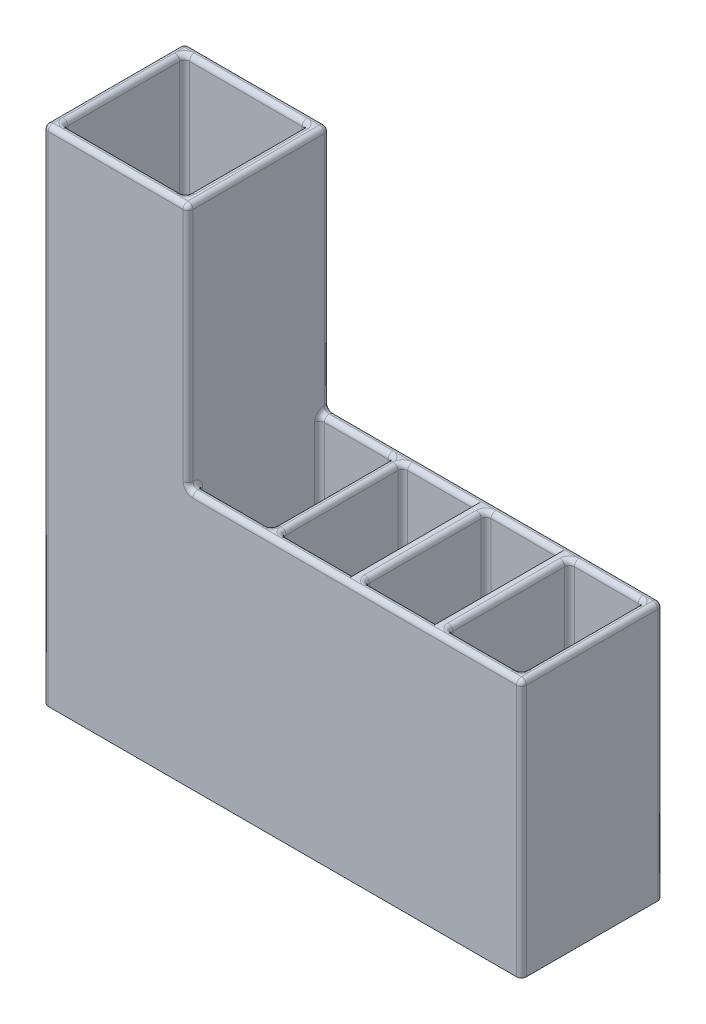
SolidWorks part; units mm, degrees
ref_plane "Front Plane" through (0, 0, 0) normal (0, 0, 1) x (1, 0, 0)
ref_plane "Top Plane" through (0, 0, 0) normal (0, 1, 0) x (1, 0, 0)
ref_plane "Right Plane" through (0, 0, 0) normal (1, 0, 0) x (0, 0, -1)
sketch "Sketch1" plane through (0, 0, 0) normal (0, 1, 0) x (1, 0, 0)
  line L0 (-61.9125, 18.288) -> (-59.3725, 15.748) construction
  line L1 (-61.9125, -18.288) -> (61.9125, -18.288)
  line L2 (-61.9125, -18.288) -> (-61.9125, 18.288)
  line L3 (-61.9125, 18.288) -> (61.9125, 18.288)
  line L4 (61.9125, -18.288) -> (61.9125, 18.288)
  line L5 (-61.9125, -18.288) -> (61.9125, 18.288) construction
  line L6 (-61.9125, 18.288) -> (61.9125, -18.288) construction
  line L7 (-59.3725, 15.748) -> (-27.6225, 15.748)
  line L8 (-59.3725, 15.748) -> (-59.3725, -15.748)
  line L9 (-59.3725, -15.748) -> (-27.6225, -15.748)
  line L10 (-27.6225, 15.748) -> (-27.6225, -15.748)
  line L11 (-59.3725, 15.748) -> (-27.6225, -15.748) construction
  line L12 (-59.3725, -15.748) -> (-27.6225, 15.748) construction
  line L13 (-61.9125, -18.288) -> (-59.3725, -15.748) construction
  line L14 (59.3725, 15.748) -> (61.9125, 18.288) construction
  line L15 (-24.4475, 15.748) -> (59.3725, 15.748)
  line L16 (-24.4475, 15.748) -> (-24.4475, -15.748)
  line L17 (-24.4475, -15.748) -> (59.3725, -15.748)
  line L18 (59.3725, 15.748) -> (59.3725, -15.748)
  line L19 (-27.6225, 15.748) -> (-24.4475, 15.748) construction
  point P0 (0, 0)
  point P6 (-43.4975, 0)
  dimension "D1" = 2.54
  dimension "D2" = 31.496
  dimension "D3" = 31.75
  dimension "D4" = 3.175
  dimension "D5" = 123.825
extrude "Boss-Extrude1" add sketch "Sketch1" along normal blind 127
sketch "Sketch2" plane through (0, 0, 0) normal (0, -1, 0) x (1, 0, 0)
  line L4 (61.9125, -18.288) -> (61.9125, 18.288)
  line L5 (61.9125, 18.288) -> (-61.9125, 18.288)
  line L6 (-61.9125, 18.288) -> (-61.9125, -18.288)
  line L7 (-61.9125, -18.288) -> (61.9125, -18.288)
  line L8 (61.9125, -18.288) -> (61.9125, 18.288)
  line L9 (61.9125, 18.288) -> (-61.9125, 18.288)
  line L10 (-61.9125, 18.288) -> (-61.9125, -18.288)
  line L11 (-61.9125, -18.288) -> (61.9125, -18.288)
  dimension "D1" = 0
extrude "Boss-Extrude2" add sketch "Sketch2" along normal blind 3.175
sketch "Sketch3" plane through (0, 127, 0) normal (0, 1, 0) x (1, 0, 0)
  line L0 (61.9125, 18.288) -> (-61.9125, 18.288) construction
  line L1 (61.9125, -18.288) -> (-24.4475, -18.288)
  line L2 (61.9125, -18.288) -> (61.9125, 18.288)
  line L3 (61.9125, 18.288) -> (-24.4475, 18.288)
  line L4 (-24.4475, -18.288) -> (-24.4475, 18.288)
  line L5 (-24.4475, 15.748) -> (-24.4475, -15.748) construction
extrude "Cut-Extrude1" cut sketch "Sketch3" against normal offset from surface (63.5 mm away) 63.5 up to face at (17.4625, 0, 0)
sketch "Sketch5" plane through (0, 0, 0) normal (0, 1, 0) x (1, 0, 0)
  line L0 (59.3725, 15.748) -> (-24.4475, 15.748) construction
  line L1 (-5.3975, 15.748) -> (-2.8575, 15.748)
  line L2 (-5.3975, 15.748) -> (-5.3975, -15.748)
  line L3 (-5.3975, -15.748) -> (-2.8575, -15.748)
  line L4 (-2.8575, 15.748) -> (-2.8575, -15.748)
  line L5 (59.3725, -15.748) -> (-24.4475, -15.748) construction
  line L6 (-24.4475, 15.748) -> (59.3725, 15.748) construction
  line L7 (16.1925, 15.748) -> (18.7325, 15.748)
  line L8 (16.1925, 15.748) -> (16.1925, -15.748)
  line L9 (16.1925, -15.748) -> (18.7325, -15.748)
  line L10 (18.7325, 15.748) -> (18.7325, -15.748)
  line L11 (37.7825, 15.748) -> (40.3225, 15.748)
  line L12 (37.7825, 15.748) -> (37.7825, -15.748)
  line L13 (37.7825, -15.748) -> (40.3225, -15.748)
  line L14 (40.3225, 15.748) -> (40.3225, -15.748)
  line L16 (-24.4475, 15.748) -> (-5.3975, -15.748) construction
  line L17 (-2.8575, -15.748) -> (16.1925, 15.748) construction
  line L18 (18.7325, 15.748) -> (37.7825, -15.748) construction
  line L19 (40.3225, -15.748) -> (59.3725, 15.748) construction
  dimension "D1" = 2.54
extrude "Boss-Extrude4" add sketch "Sketch5" along normal up to surface (63.5 mm away) up to face at (18.0975, 63.5, 0)
sketch "Sketch6" plane through (0, 0, 0) normal (0, 1, 0) x (1, 0, 0)
  line L0 (-59.3725, -15.748) -> (-27.6225, 15.748) construction
  line L1 (-2.8575, -15.748) -> (16.1925, 15.748) construction
  line L2 (40.3225, -15.748) -> (59.3725, 15.748) construction
  point P12 (-43.4975, 0)
  point P13 (6.6675, 0)
  point P14 (49.8475, 0)
fillet "Fillet1" radius 1.27 66 edges at (-24.4475, 95.25, 18.288) (-24.4475, 95.25, -18.288) (49.8475, 0, 15.748) (49.8475, 63.5, 15.748) (49.8475, 63.5, -15.748) (49.8475, 0, -15.748) (6.6675, 63.5, 15.748) (6.6675, 0, 15.748) (6.6675, 0, -15.748) (6.6675, 63.5, -15.748) (28.2575, 63.5, 15.748) (28.2575, 0, 15.748) (28.2575, 0, -15.748) (28.2575, 63.5, -15.748) (-43.4975, 127, 15.748) (-43.4975, 127, -15.748) (-14.9225, 63.5, 15.748) (-14.9225, 0, 15.748) (-14.9225, 0, -15.748) (-14.9225, 63.5, -15.748) (-61.9125, 127, 0) (-43.18, 127, -18.288) (-24.4475, 127, 0) (-43.18, 127, 18.288) (-24.4475, 0, 0) (-5.3975, 0, 0) (40.3225, 31.75, 15.748) (40.3225, 63.5, 0) (40.3225, 0, 0) (40.3225, 31.75, -15.748) (59.3725, 31.75, 15.748) (59.3725, 31.75, -15.748) (59.3725, 63.5, 0) (59.3725, 0, 0) (16.1925, 0, 0) (37.7825, 0, 0) (-2.8575, 0, 0) (-2.8575, 31.75, 15.748) (-2.8575, 63.5, 0) (-2.8575, 31.75, -15.748) (18.7325, 0, 0) (18.7325, 31.75, 15.748) (18.7325, 63.5, 0) (18.7325, 31.75, -15.748) (-27.6225, 63.5, -15.748) (-27.6225, 127, 0) (-27.6225, 63.5, 15.748) (-59.3725, 63.5, 15.748) (-59.3725, 127, 0) (-59.3725, 63.5, -15.748) (-43.4975, 0, -15.748) (-27.6225, 0, 0) (-43.4975, 0, 15.748) (-59.3725, 0, 0) (61.9125, 30.1625, 18.288) (-61.9125, 61.9125, -18.288) (-61.9125, 61.9125, 18.288) (18.7325, 63.5, -18.288) (18.7325, 63.5, 18.288) (61.9125, 63.5, 0) (61.9125, 30.1625, -18.288) (-5.3975, 63.5, 0) (-5.3975, 31.75, 15.748) (-24.4475, 31.75, 15.748) (-5.3975, 31.75, -15.748) (-24.4475, 31.75, -15.748)
hole_wizard "CSK for #10 Flat Head Machine Screw (100)1" positions "3DSketch1" profile "Sketch7" countersink size "#10" standard "ANSI Inch" end condition through all
sketch3d "3DSketch1"
  point P0 (-43.4975, 0, 0)
  point P3 (6.6675, 0, 0)
  point P6 (49.8475, 0, 0)
sketch "Sketch7" plane through (-43.4975, 0, 0) normal (1, 0, 0) x (0, 0, 1)
  line L0 (0, 0) -> (0, 3.175)
  line L1 (0, 3.175) -> (2.5527, 3.175)
  line L2 (2.5527, 3.175) -> (2.5527, 1.9608)
  line L3 (2.5527, 1.9608) -> (4.8895, 0)
  line L5 (4.8895, 0) -> (0, 0)
  line L6 (-2.5527, 1.9608) -> (-4.8895, 0) construction
  line L11 (0, -6.35) -> (0, 107.95) construction
  dimension "Thru Hole Dia." = 5.1054
  dimension "Thru Hole Depth" = 3.175
  dimension "Near C'Sink Dia." = 9.779
  dimension "Near C'Sink Angle" = 100
